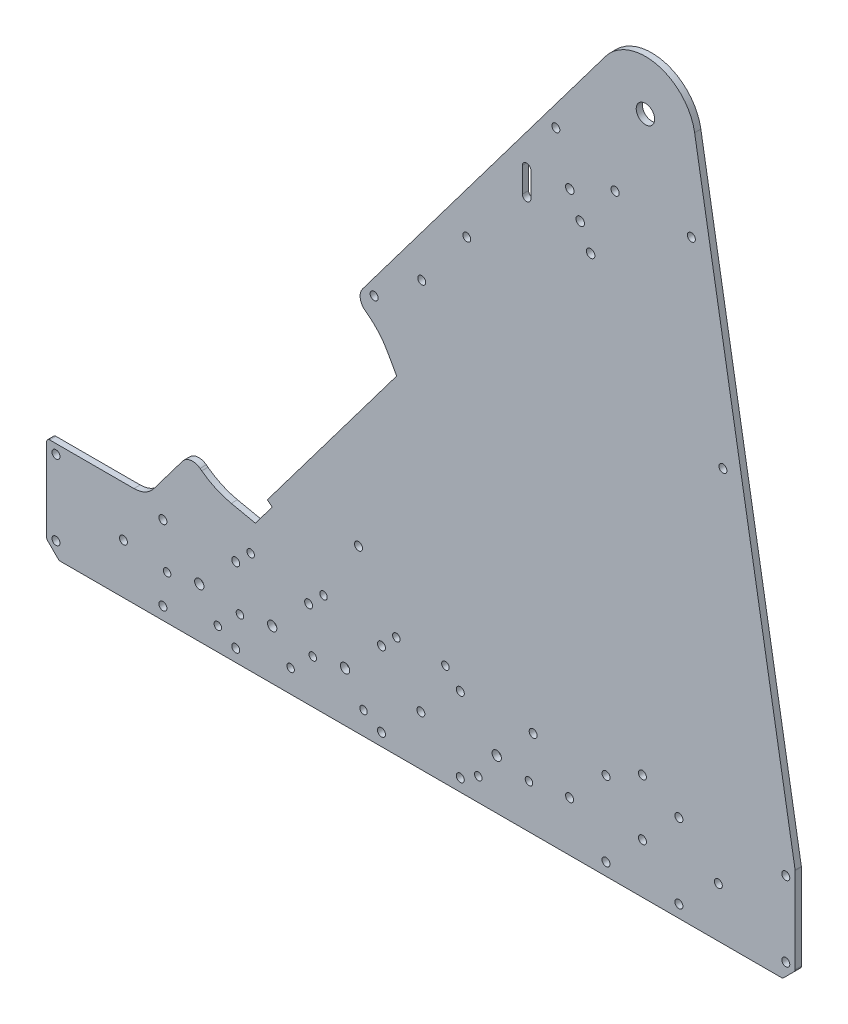
SolidWorks part; units mm, degrees
ref_plane "Front Plane" through (0, 0, 0) normal (0, 0, 1) x (1, 0, 0)
ref_plane "Top Plane" through (0, 0, 0) normal (0, 1, 0) x (1, 0, 0)
ref_plane "Right Plane" through (0, 0, 0) normal (1, 0, 0) x (0, 0, -1)
sketch "Sketch1" plane through (0, 0, 0) normal (0, 0, 1) x (1, 0, 0)
  line L1 (0, 0) -> (381, 0)
  line L2 (0, 0) -> (0, 50.8)
  line L4 (381, 0) -> (381, 50.8)
  line L5 (381, 50.8) -> (329.8374, 350.3513)
  line L6 (0, 50.8) -> (44.463, 50.8)
  line L7 (54.6105, 55.8634) -> (73.025, 80.3327)
  line L9 (112.3265, 79.755) -> (178.1676, 167.245)
  line L11 (157.0275, 191.9556) -> (284.5049, 361.3482)
  line L12 (112.3265, 79.755) -> (114.8634, 77.8458)
  line L13 (114.8634, 77.8458) -> (106.2722, 66.4299)
  line L14 (157.0275, 191.9556) -> (169.7119, 182.4098)
  line L15 (169.7119, 182.4098) -> (178.1676, 167.245)
  line L16 (73.025, 80.3327) -> (85.7094, 70.7869)
  line L17 (85.7094, 70.7869) -> (106.2722, 66.4299)
  line L18 (169.7119, 182.4098) -> (85.7094, 70.7869) construction
  arc A0 (284.5049, 361.3482) -> (329.8374, 350.3513) centre (304.8, 346.075) cw
  arc A1 (44.463, 50.8) -> (54.6105, 55.8634) centre (44.463, 63.5) ccw
  point P11 (50.8, 50.8)
  dimension "D4" = 346.075
  dimension "D7" = 12.7
  dimension "D5" = 25.4
  dimension "D1" = 50.8
  dimension "D2" = 381
  dimension "D3" = 76.2
  dimension "D6" = 50.8
  dimension "D8" = 123.825
  dimension "D9" = 139.7
  dimension "D10" = 15.875
  dimension "D11" = 31.75
  dimension "D12" = 73.025
  dimension "D13" = 3.175
  dimension "D14" = 14.2875
  dimension "D15" = 115
extrude "Boss-Extrude1" add sketch "Sketch1" along normal blind 3.175
sketch "Sketch2" plane through (0, 0, 3.175) normal (0, 0, 1) x (1, 0, 0)
  line L1 (190.5, 50.8) -> (190.5, 0) construction
  line L3 (0, 0) -> (381, 0) construction
  line L5 (0, 6.35) -> (0, 0)
  line L6 (0, 50.8) -> (0, 0) construction
  line L7 (0, 0) -> (6.35, 0)
  line L8 (6.35, 0) -> (0, 6.35)
  line L9 (381, 0) -> (374.65, 0)
  line L10 (374.65, 0) -> (381, 6.35)
  line L11 (381, 6.35) -> (381, 0)
  circle A19 centre (4.7625, 46.0375) radius 2.032
  circle A20 centre (4.7625, 7.9375) radius 2.032
  circle A21 centre (376.2375, 7.9375) radius 2.032
  circle A22 centre (376.2375, 46.0375) radius 2.032
  dimension "D21" = 6.35
  dimension "D27" = 4.064
  dimension "D4" = 46.0375
  dimension "D22" = 6.35
  dimension "D25" = 4.7625
  dimension "D28" = 7.9375
extrude "Cut-Extrude1" cut sketch "Sketch2" against normal up to next
sketch "Sketch5" plane through (0, 0, 3.175) normal (0, 0, 1) x (1, 0, 0)
  line L0 (151.892, 25.4) -> (229.108, 25.4) construction
  line L1 (229.108, 25.4) -> (341.884, 25.4) construction
  circle A0 centre (39.116, 25.4) radius 2.032
  circle A1 centre (59.182, 6.35) radius 2.032
  circle A2 centre (59.182, 44.45) radius 2.032
  circle A3 centre (96.266, 44.45) radius 2.032
  circle A4 centre (133.35, 44.45) radius 2.032
  circle A5 centre (170.434, 44.45) radius 2.032
  circle A6 centre (210.566, 44.45) radius 2.032
  circle A7 centre (210.566, 6.35) radius 2.032
  circle A8 centre (170.434, 6.35) radius 2.032
  circle A9 centre (247.65, 44.45) radius 2.032
  circle A10 centre (266.192, 25.4) radius 2.032
  circle A11 centre (39.116, 25.4) radius 2.286 construction
  circle A12 centre (59.182, 44.45) radius 1.905 construction
  circle A13 centre (59.182, 6.35) radius 1.905 construction
  circle A14 centre (96.266, 44.45) radius 1.905 construction
  circle A15 centre (133.35, 44.45) radius 1.905 construction
  circle A16 centre (170.434, 44.45) radius 1.905 construction
  circle A17 centre (170.434, 6.35) radius 2.159 construction
  circle A18 centre (210.566, 6.35) radius 2.159 construction
  circle A19 centre (210.566, 44.45) radius 1.905 construction
  circle A20 centre (247.65, 44.45) radius 1.905 construction
  circle A21 centre (266.192, 25.4) radius 2.286 construction
  circle A22 centre (77.724, 25.4) radius 2.3813
  circle A23 centre (114.808, 25.4) radius 2.3813
  circle A24 centre (151.892, 25.4) radius 2.3813
  circle A25 centre (229.108, 25.4) radius 2.3813
  circle A26 centre (190.5, 25.4) radius 2.032
  circle A28 centre (303.276, 25.4) radius 2.032
  circle A29 centre (341.884, 25.4) radius 2.032
  circle A30 centre (77.724, 25.4) radius 7.366 construction
  circle A31 centre (114.808, 25.4) radius 7.366 construction
  circle A32 centre (151.892, 25.4) radius 7.366 construction
  circle A33 centre (229.108, 25.4) radius 7.366 construction
  dimension "D1" = 4.064
  dimension "D2" = 4.7625
  dimension "D3" = 37.084
  dimension "D4" = 38.608
  dimension "D5" = 38.608
extrude "Cut-Extrude4" cut sketch "Sketch5" against normal through all
sketch "Sketch6" plane through (0, 0, 3.175) normal (0, 0, 1) x (1, 0, 0)
  line L0 (6.35, 0) -> (374.65, 0) construction
  line L1 (266.192, 25.4) -> (303.276, 25.4) construction
  line L2 (284.734, 6.35) -> (284.734, 44.45) construction
  line L3 (151.892, 25.4) -> (114.808, 25.4) construction
  line L4 (114.808, 25.4) -> (77.724, 25.4) construction
  circle A0 centre (284.734, 44.45) radius 2.032
  circle A1 centre (284.734, 6.35) radius 2.032
  circle A2 centre (321.818, 6.35) radius 2.032
  circle A3 centre (321.818, 44.45) radius 2.032
  circle A4 centre (96.266, 6.35) radius 2.032
  circle A6 centre (303.276, 53.975) radius 2.032
  arc A7 (304.329, 52.3875) -> (302.223, 52.3875) centre (303.276, 53.975) ccw construction
  point P8 (284.734, 25.4)
  point P9 (284.734, 25.4)
  point P28 (96.266, 25.4)
  dimension "D1" = 4.064
  dimension "D2" = 6.35
  dimension "D3" = 37.084
extrude "Cut-Extrude5" cut sketch "Sketch6" against normal through all
sketch "Sketch3" plane through (0, 0, 3.175) normal (0, 0, 1) x (1, 0, 0)
  line L0 (73.025, 80.3327) -> (54.6105, 55.8634) construction
  line L1 (381, 6.35) -> (381, 50.8) construction
  line L2 (6.35, 0) -> (374.65, 0) construction
  line L3 (304.8, 346.075) -> (289.3732, 304.3879) construction
  line L4 (266.2957, 293.7771) -> (289.3732, 304.3879) construction
  line L5 (266.2957, 293.7771) -> (271.6011, 282.2383) construction
  line L6 (271.6011, 282.2383) -> (276.9065, 270.6996) construction
  line L7 (381, 50.8) -> (329.8374, 350.3513) construction
  line L8 (244.3127, 279.4) -> (244.3127, 292.1) construction
  line L9 (0, 50.8) -> (0, 6.35) construction
  line L12 (284.5049, 361.3482) -> (157.0275, 191.9556) construction
  line L13 (242.1537, 279.4) -> (242.1537, 292.1)
  line L14 (246.4717, 279.4) -> (246.4717, 292.1)
  line L15 (190.9415, 215.9) -> (213.8513, 246.3426) construction
  circle A0 centre (304.8, 346.075) radius 4.699
  circle A1 centre (166.6875, 196.85) radius 2.032
  circle A2 centre (158.75, 82.55) radius 2.032
  circle A3 centre (289.3732, 304.3879) radius 2.0955
  circle A5 centre (266.2957, 293.7771) radius 2.159
  circle A6 centre (271.6011, 282.2383) radius 2.159
  circle A7 centre (276.9065, 270.6996) radius 2.159
  circle A8 centre (328.1868, 303.4404) radius 2.032
  circle A9 centre (344.223, 209.55) radius 2.032
  circle A12 centre (259.2118, 317.1783) radius 2.032
  arc A26 (242.1537, 279.4) -> (246.4717, 279.4) centre (244.3127, 279.4) ccw
  arc A27 (246.4717, 292.1) -> (242.1537, 292.1) centre (244.3127, 292.1) ccw
  circle A28 centre (213.8513, 246.3426) radius 2.032
  circle A29 centre (190.9415, 215.9) radius 2.032
  point P27 (244.3127, 285.75)
  dimension "D1" = 9.398
  dimension "D3" = 4.064
  dimension "D6" = 4.064
  dimension "D11" = 4.318
  dimension "D10" = 4.191
  dimension "D13" = 4.064
  dimension "D20" = 4.064
  dimension "D18" = 2.159
  dimension "D28" = 12.7
  dimension "D21" = 38.1
  dimension "D19" = 9.525
  dimension "D29" = 4.064
  dimension "D4" = 222.25
  dimension "D5" = 82.55
  dimension "D7" = 25.4
  dimension "D8" = 12.7
  dimension "D9" = 44.45
  dimension "D12" = 12.7
  dimension "D14" = 9.525
  dimension "D15" = 9.525
  dimension "D16" = 95.25
  dimension "D17" = 209.55
  dimension "D22" = 12.7
  dimension "D23" = 53.975
  dimension "D24" = 6.35
  dimension "D25" = 196.85
  dimension "D26" = 166.6875
  dimension "D27" = 279.4
  dimension "D30" = 30
  dimension "D31" = 135
  dimension "D32" = 215.9
extrude "Cut-Extrude2" cut sketch "Sketch3" against normal through all
fillet "Fillet1" radius 1.5875 6 edges at (374.65, 0, 1.5875) (381, 6.35, 1.5875) (381, 50.8, 1.5875) (6.35, 0, 1.5875) (0, 6.35, 1.5875) (0, 50.8, 1.5875)
sketch "Sketch4" plane through (0, 0, 0) normal (0, 0, -1) x (-1, 0, 0)
  circle A0 centre (-61.3181, 22.2981) radius 1.905 construction
  circle A1 centre (-87.1313, 11.606) radius 1.905 construction
  circle A2 centre (-98.4021, 22.2981) radius 1.905 construction
  circle A3 centre (-124.2153, 11.606) radius 1.905 construction
  circle A4 centre (-135.4861, 22.2981) radius 1.905 construction
  circle A5 centre (-161.2993, 11.606) radius 1.905 construction
  circle A6 centre (-245.5139, 22.2981) radius 1.905 construction
  circle A7 centre (-219.7007, 11.606) radius 1.905 construction
  circle A8 centre (-202.982, 51.9684) radius 1.905 construction
  circle A9 centre (-178.018, 51.9684) radius 1.905 construction
  circle A10 centre (-140.934, 51.9684) radius 1.905 construction
  circle A11 centre (-103.85, 51.9684) radius 1.905 construction
  circle A12 centre (-61.3181, 22.2981) radius 1.905
  circle A13 centre (-87.1313, 11.606) radius 1.905
  circle A14 centre (-98.4021, 22.2981) radius 1.905
  circle A15 centre (-124.2153, 11.606) radius 1.905
  circle A16 centre (-135.4861, 22.2981) radius 1.905
  circle A17 centre (-161.2993, 11.606) radius 1.905
  circle A18 centre (-245.5139, 22.2981) radius 1.905
  circle A19 centre (-219.7007, 11.606) radius 1.905
  circle A20 centre (-202.982, 51.9684) radius 1.905
  circle A21 centre (-178.018, 51.9684) radius 1.905
  circle A22 centre (-140.934, 51.9684) radius 1.905
  circle A23 centre (-103.85, 51.9684) radius 1.905
extrude "Cut-Extrude3" cut sketch "Sketch4" against normal up to next
fillet "Fillet2" radius 38.1 2 edges at (85.7094, 70.7869, 1.5875) (169.7119, 182.4098, 1.5875)
fillet "Fillet3" radius 6.35 2 edges at (73.025, 80.3327, 1.5875) (157.0275, 191.9556, 1.5875)
